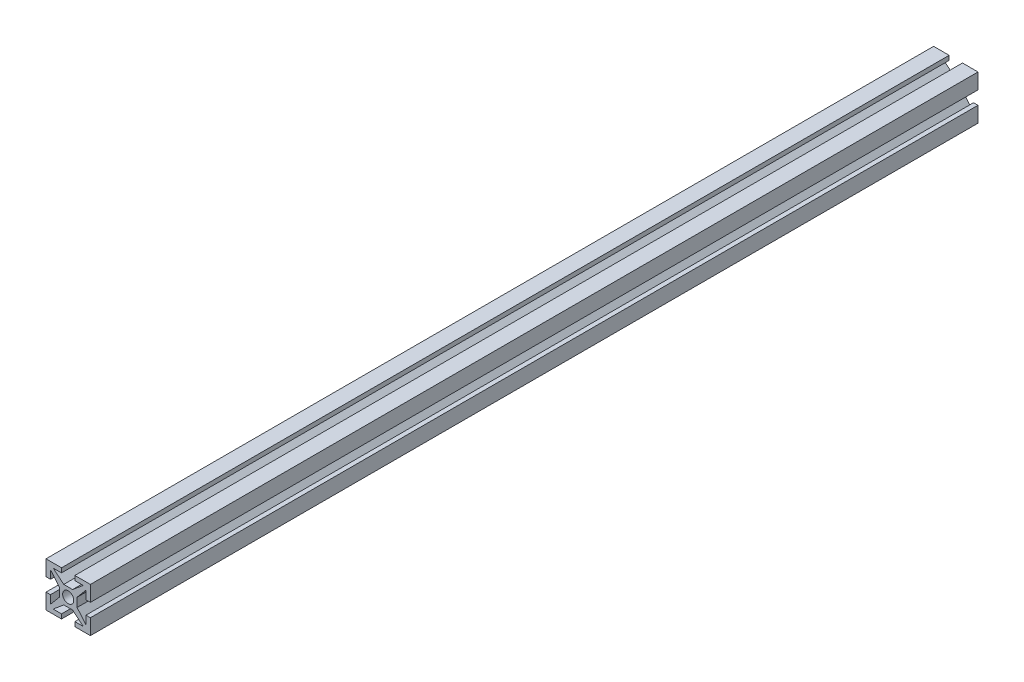
SolidWorks part; units mm, degrees
ref_plane "Front Plane" through (0, 0, 0) normal (0, 0, 1) x (1, 0, 0)
ref_plane "Top Plane" through (0, 0, 0) normal (0, 1, 0) x (1, 0, 0)
ref_plane "Right Plane" through (0, 0, 0) normal (1, 0, 0) x (0, 0, -1)
sketch "Esquisse2" plane through (0, 0, 0) normal (0, 0, 1) x (1, 0, 0)
  line L0 (-1, -2) -> (1, -2)
  line L1 (1, -2) -> (3.3835, -4)
  line L2 (3.3835, -4) -> (1.5, -4)
  line L3 (1.5, -4) -> (1.5, -5)
  line L4 (1.5, -5) -> (5, -5)
  line L5 (-1, -2) -> (-3.3835, -4)
  line L6 (-3.3835, -4) -> (-1.5, -4)
  line L7 (-1.5, -4) -> (-1.5, -5)
  line L8 (-1.5, -5) -> (-5, -5)
  line L9 (-5, -5) -> (-5, -1.5)
  line L10 (-5, -1.5) -> (-4, -1.5)
  line L11 (-4, -1.5) -> (-4, -3.3835)
  line L12 (-4, -3.3835) -> (-2, -1)
  line L13 (-2, -1) -> (-2, 1)
  line L14 (-2, 1) -> (-4, 3.3835)
  line L15 (-4, 3.3835) -> (-4, 1.5)
  line L16 (-4, 1.5) -> (-5, 1.5)
  line L17 (-5, 1.5) -> (-5, 5)
  line L18 (-5, 5) -> (-1.5, 5)
  line L19 (-1.5, 5) -> (-1.5, 4)
  line L20 (-1.5, 4) -> (-3.3835, 4)
  line L21 (-3.3835, 4) -> (-1, 2)
  line L22 (-1, 2) -> (1, 2)
  line L23 (1, 2) -> (3.3835, 4)
  line L24 (3.3835, 4) -> (1.5, 4)
  line L25 (1.5, 4) -> (1.5, 5)
  line L26 (1.5, 5) -> (5, 5)
  line L27 (5, 5) -> (5, 1.5)
  line L28 (5, 1.5) -> (4, 1.5)
  line L29 (4, 1.5) -> (4, 3.3835)
  line L30 (4, 3.3835) -> (2, 1)
  line L31 (2, -1) -> (2, 1)
  line L32 (2, -1) -> (4, -3.3835)
  line L33 (4, -3.3835) -> (4, -1.5)
  line L34 (4, -1.5) -> (5, -1.5)
  line L35 (5, -1.5) -> (5, -5)
  circle A0 centre (0, 0) radius 1.25
  point P4 (0, -2)
  point P34 (0, 2)
  point P40 (2, 0)
  dimension "D4" = 2.5
  dimension "D1" = 2
  dimension "D2" = 3.5
  dimension "D3" = 1
  dimension "D5" = 10
  dimension "D6" = 10
  dimension "D7" = 140
  dimension "D8" = 4
  dimension "D9" = 4
  dimension "D10" = 3.5
  dimension "D11" = 3
extrude "Main Extrusion" add sketch "Esquisse2" along normal blind 200
